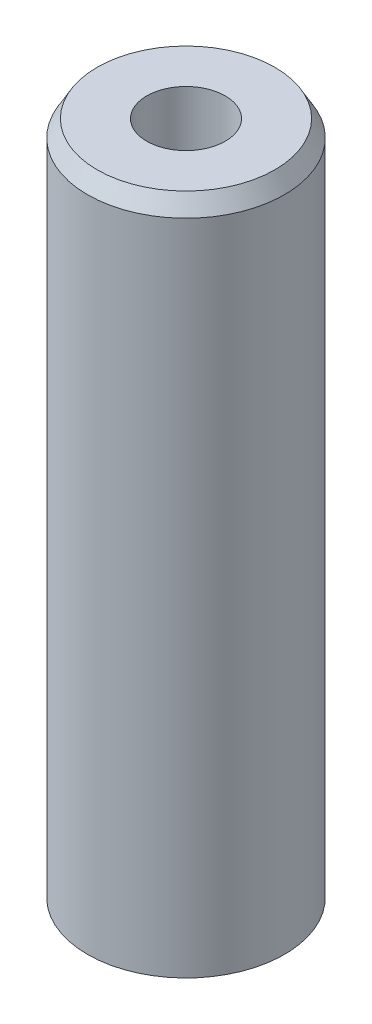
SolidWorks part; units mm, degrees
ref_plane "Front Plane" through (0, 0, 0) normal (0, 0, 1) x (1, 0, 0)
ref_plane "Top Plane" through (0, 0, 0) normal (0, 1, 0) x (1, 0, 0)
ref_plane "Right Plane" through (0, 0, 0) normal (1, 0, 0) x (0, 0, -1)
sketch "Sketch1" plane through (0, 0, 0) normal (0, 1, 0) x (1, 0, 0)
  circle A0 centre (0, 0) radius 35
  dimension "SHAFT_OD" = 70
extrude "Boss-Extrude1" add sketch "Sketch1" along normal blind 243.1769
sketch "Sketch2" plane through (0, 0, 0) normal (0, 1, 0) x (1, 0, 0)
  circle A0 centre (0, 0) radius 13.9653
  dimension "BORE_D" = 27.9305
extrude "Cut-Extrude1" cut sketch "Sketch2" along normal through all
chamfer "Chamfer1" distance 5.9413 angle 30 2 edges at (0, 243.1769, 35) (0, 0, 35) first distance on face at (0, 243.1769, 35) first distance on face at (0, 0, 13.9653)
